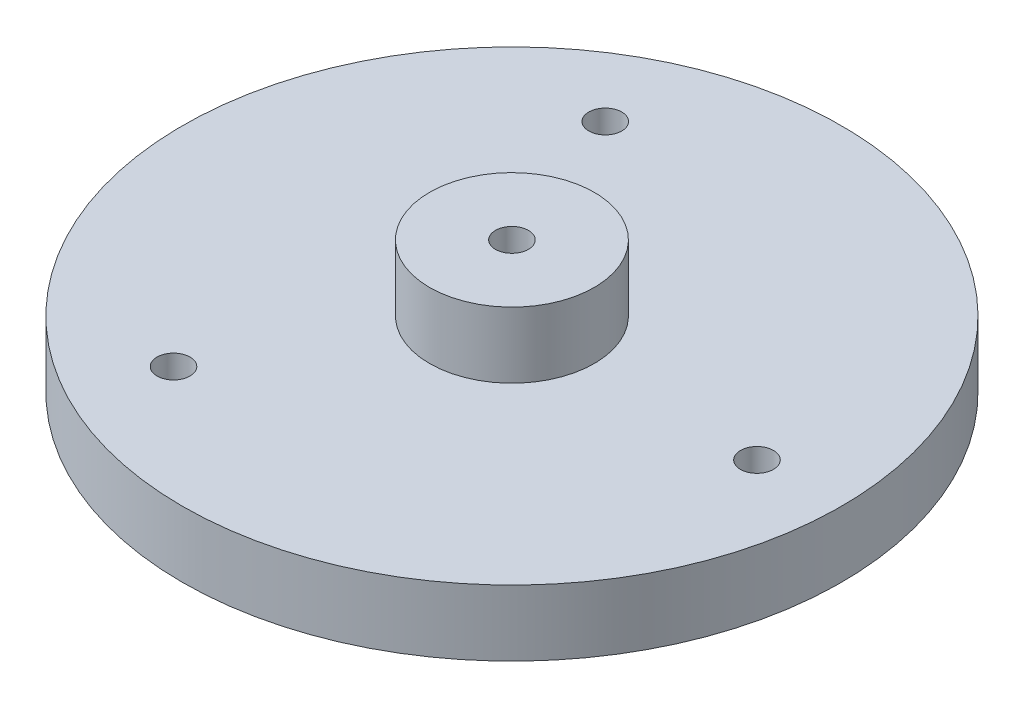
SolidWorks part; units mm, degrees
ref_plane "Front Plane" through (0, 0, 0) normal (0, 0, 1) x (1, 0, 0)
ref_plane "Top Plane" through (0, 0, 0) normal (0, 1, 0) x (1, 0, 0)
ref_plane "Right Plane" through (0, 0, 0) normal (1, 0, 0) x (0, 0, -1)
sketch "Sketch1" plane through (0, 0, 0) normal (0, 1, 0) x (1, 0, 0)
  circle A0 centre (0, 0) radius 5
  circle A1 centre (0, 0) radius 25
  circle A2 centre (0, 0) radius 100
  circle A3 centre (-36.9417, 65.2711) radius 5
  circle A6 centre (74.9972, -0.6431) radius 5
  circle A7 centre (-38.0556, -64.628) radius 5
  circle A8 centre (0, 0) radius 75
  dimension "D1" = 10
  dimension "D2" = 50
  dimension "D3" = 200
  dimension "D4" = 10
  dimension "D5" = 75
  dimension "D6" = 3
extrude "Boss-Extrude1" add sketch "Sketch1" along normal blind 20 contours A2 A7 A6 A3 A1 | A6 A8 A3 A7 A1 region at (-97.1716, 0, 0) region at (-30.0268, 0, -66.9694)
extrude "Boss-Extrude2" add sketch "Sketch1<3>" along normal blind 40 contours A1 A0 region at (-24.2929, 0, 0)
sketch "Sketch1<3>" plane through (0, 0, 0) normal (0, 1, 0) x (1, 0, 0) same geometry as "Sketch1"
